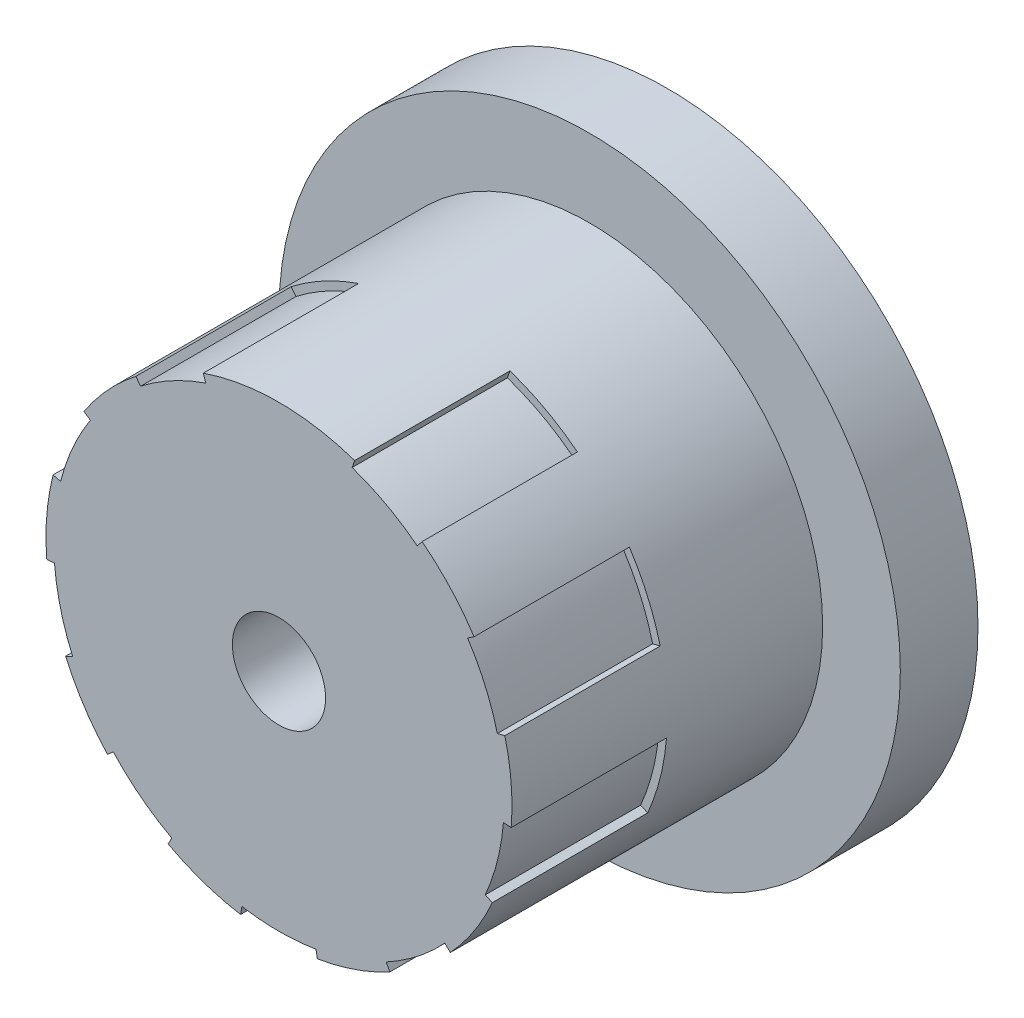
SolidWorks part; units mm, degrees
ref_plane "Front Plane" through (0, 0, 0) normal (0, 0, 1) x (1, 0, 0)
ref_plane "Top Plane" through (0, 0, 0) normal (0, 1, 0) x (1, 0, 0)
ref_plane "Right Plane" through (0, 0, 0) normal (1, 0, 0) x (0, 0, -1)
sketch "Sketch1" plane through (0, 0, 0) normal (0, 0, 1) x (1, 0, 0)
  line L24 (0, 0) -> (0, 15)
  line L25 (0, 0) -> (4.8705, 14.1873)
  line L26 (0, 0) -> (9.2132, 11.8371)
  line L27 (0, 0) -> (12.5575, 8.2042)
  line L28 (0, 0) -> (14.541, 3.6823)
  line L29 (0, 0) -> (14.9488, -1.2387)
  line L30 (0, 0) -> (13.7366, -6.0254)
  line L31 (0, 0) -> (11.0359, -10.1592)
  line L32 (0, 0) -> (7.1392, -13.1921)
  line L33 (0, 0) -> (2.4689, -14.7954)
  line L34 (0, 0) -> (-2.4689, -14.7954)
  line L35 (0, 0) -> (-7.1392, -13.1921)
  line L36 (0, 0) -> (-11.0359, -10.1592)
  line L37 (0, 0) -> (-13.7366, -6.0254)
  line L38 (0, 0) -> (-14.9488, -1.2387)
  line L39 (0, 0) -> (-14.541, 3.6823)
  line L40 (0, 0) -> (-12.5575, 8.2042)
  line L41 (0, 0) -> (-9.2132, 11.8371)
  line L42 (0, 0) -> (-4.8705, 14.1873)
  circle A25 centre (0, 0) radius 15
  circle A26 centre (0, 0) radius 14.5
  circle A27 centre (0, 0) radius 20
  point P27 (0, 0)
  point P31 (0, 0)
  dimension "D2" = 30
  dimension "D3" = 29
  dimension "D5" = 40
  dimension "D4" = 19
extrude "Boss-Extrude1" add sketch "Sketch1" along normal blind 20 contours A26 L24 A25 L42 | A26 L25 A25 L24 | A26 L27 A25 L26 | A26 L29 A25 L28 | A26 L31 A25 L30 | A26 L33 A25 L32 | A26 L35 A25 L34 | A26 L37 A25 L36 | A26 L39 A25 L38 | A26 L41 A25 L40 | A26 region at (-2.417, 14.484, 0) region at (2.417, 14.484, 0) region at (10.8036, 9.9454, 0) region at (14.6341, 1.2126, 0) region at (12.2932, -8.0315, 0) region at (4.768, -13.8887, 0) region at (-4.768, -13.8887, 0) region at (-12.2932, -8.0315, 0) region at (-14.6341, 1.2126, 0) region at (-10.8036, 9.9454, 0)
extrude "Boss-Extrude5" add sketch "Sketch1<7>" against normal blind 5 contours A27 A25 | A25 region at (-19.4343, 0, 0)
sketch "Sketch1<7>" plane through (0, 0, 0) normal (0, 0, 1) x (1, 0, 0) same geometry as "Sketch1"
sketch "Sketch4" plane through (0, 0, 0) normal (0, 0, 1) x (1, 0, 0)
  circle A0 centre (0, 0) radius 15
  circle A1 centre (0, 0) radius 14.5
extrude "Boss-Extrude6" add sketch "Sketch4" along normal blind 10
sketch "Sketch5" plane through (0, 0, 20) normal (0, 0, 1) x (1, 0, 0)
  circle A0 centre (0, 0) radius 3
  dimension "D1" = 6
extrude "Cut-Extrude1" cut sketch "Sketch5" against normal blind 20
